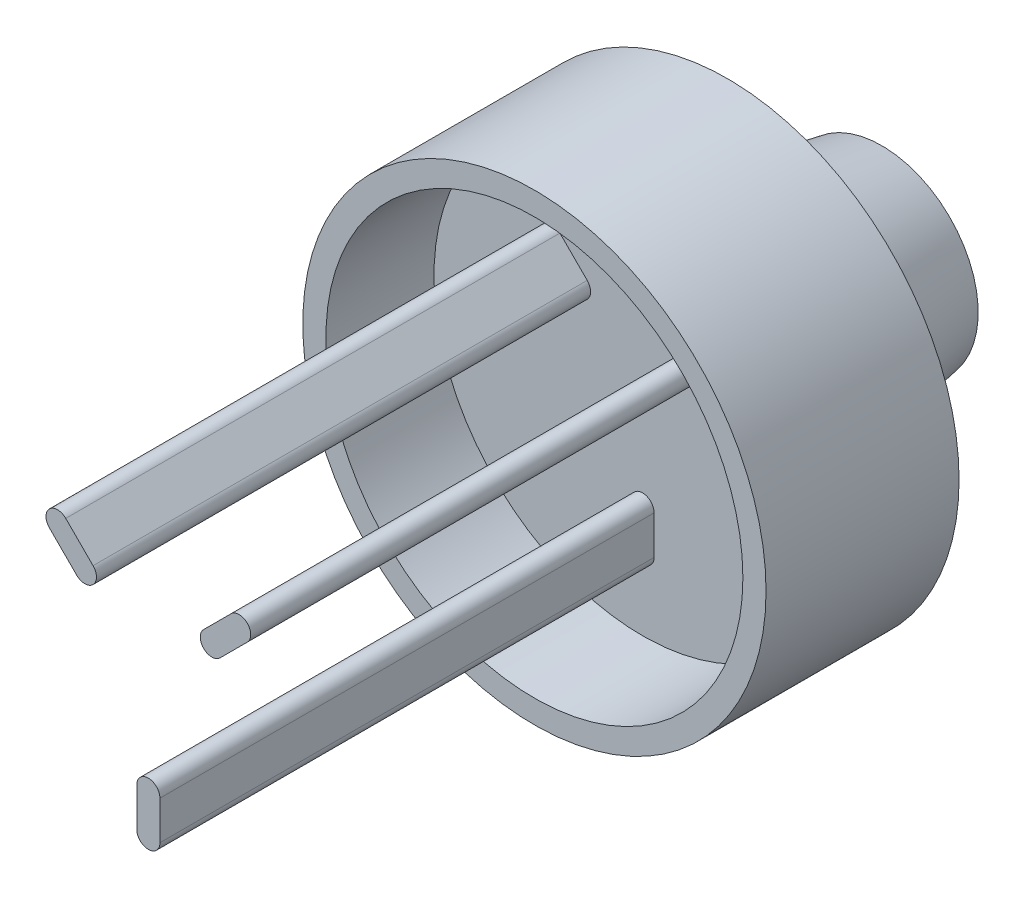
SolidWorks part; units mm, degrees
material "ABS"
ref_plane "Front Plane" through (0, 0, 0) normal (0, 0, 1) x (1, 0, 0)
ref_plane "Top Plane" through (0, 0, 0) normal (0, 1, 0) x (1, 0, 0)
ref_plane "Right Plane" through (0, 0, 0) normal (1, 0, 0) x (0, 0, -1)
sketch "Circle" plane through (0, 0, 0) normal (0, 0, 1) x (1, 0, 0)
  circle A0 centre (0, 0) radius 7.62
extrude "Boss-Extrude3" add sketch "Circle" along normal mid plane 6.35
sketch "Inner Circle" plane through (0, 0, 3.175) normal (0, 0, 1) x (1, 0, 0)
  circle A0 centre (0, 0) radius 6.858
extrude "Cut-Extrude1" cut sketch "Inner Circle" against normal blind 3.556
sketch "Back Circle" plane through (0, 0, -3.175) normal (0, 0, -1) x (-1, 0, 0)
  circle A0 centre (0, 0) radius 4.064
extrude "Boss-Extrude4" add sketch "Back Circle" along normal blind 5.08 draft 10
sketch "Prongs" plane through (0, 0, -0.381) normal (0, 0, 1) x (1, 0, 0)
  line L0 (2.9866, 2.9866) -> (2.0885, 2.0885) construction
  line L4 (2.7172, 3.256) -> (1.8191, 2.358)
  line L5 (3.256, 2.7172) -> (2.358, 1.8191)
  line L6 (-2.9866, 2.9866) -> (-2.0885, 2.0885) construction
  line L7 (-2.7172, 3.256) -> (-1.8191, 2.358)
  line L8 (-3.256, 2.7172) -> (-2.358, 1.8191)
  line L9 (0, -4.4354) -> (0, -3.1654) construction
  line L10 (-0.381, -4.4354) -> (-0.381, -3.1654)
  line L11 (0.381, -4.4354) -> (0.381, -3.1654)
  arc A2 (-2.7172, 3.256) -> (-3.256, 2.7172) centre (-2.9866, 2.9866) ccw
  arc A3 (-2.358, 1.8191) -> (-1.8191, 2.358) centre (-2.0885, 2.0885) ccw
  arc A4 (-0.381, -4.4354) -> (0.381, -4.4354) centre (0, -4.4354) ccw
  arc A5 (0.381, -3.1654) -> (-0.381, -3.1654) centre (0, -3.1654) ccw
  arc A10 (2.7172, 3.256) -> (3.256, 2.7172) centre (2.9866, 2.9866) cw
  arc A11 (2.358, 1.8191) -> (1.8191, 2.358) centre (2.0885, 2.0885) cw
  point P2 (2.5376, 2.5376)
  point P15 (-2.5376, 2.5376)
  point P22 (0, -3.8004)
extrude "Boss-Extrude5" add sketch "Prongs" along normal blind 16.256
